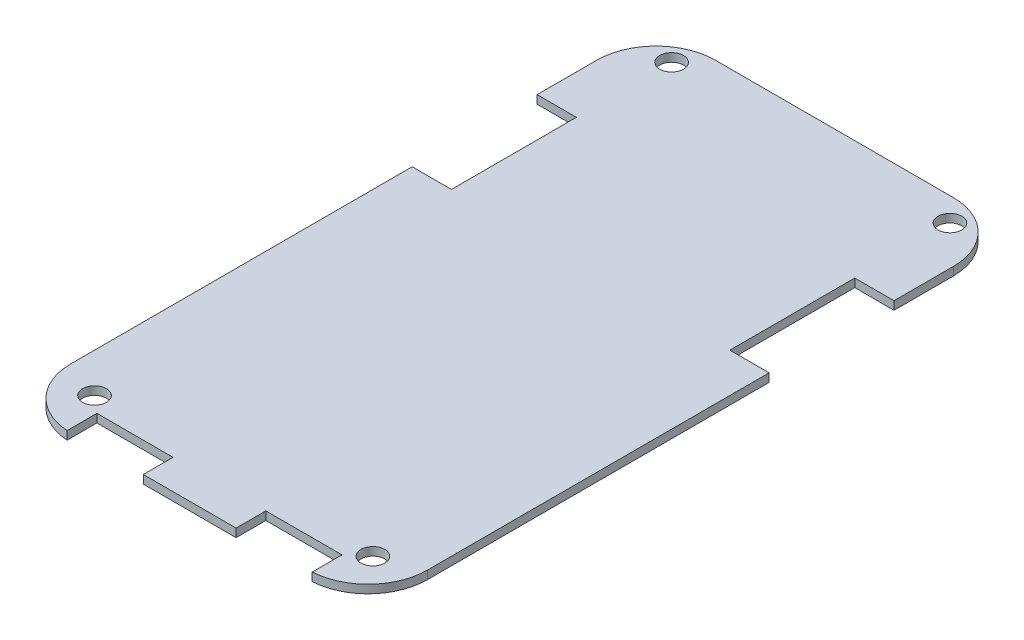
SolidWorks part; units mm, degrees
material "A-Glass Fiber"
ref_plane "Front Plane" through (0, 0, 0) normal (0, 0, 1) x (1, 0, 0)
ref_plane "Top Plane" through (0, 0, 0) normal (0, 1, 0) x (1, 0, 0)
ref_plane "Right Plane" through (0, 0, 0) normal (1, 0, 0) x (0, 0, -1)
sketch "Sketch2" plane through (0, 0, 0) normal (0, 1, 0) x (1, 0, 0)
  line L1 (-15, 27.1) -> (15, 27.1)
  line L2 (-15, 27.1) -> (-15, -27.1)
  line L3 (-15, -27.1) -> (15, -27.1)
  line L4 (15, 27.1) -> (15, -27.1)
  dimension "D1" = 30
  dimension "D2" = 54.2
  dimension "D3" = 15
  dimension "D4" = 27.1
extrude "CircuitBoard" add sketch "Sketch2" along normal blind 0.7
sketch "Sketch3" plane through (0, 0.7, 0) normal (0, 1, 0) x (1, 0, 0)
  line L0 (15, 27.1) -> (-15, 27.1) construction
  line L1 (-15, 17.1) -> (-11.7, 17.1)
  line L2 (-15, 17.1) -> (-15, 6.6)
  line L3 (-15, 6.6) -> (-11.7, 6.6)
  line L4 (-11.7, 17.1) -> (-11.7, 6.6)
  line L5 (-15, 27.1) -> (-15, -27.1) construction
  line L6 (-15, -27.1) -> (15, -27.1) construction
  line L7 (-10.3, -24.6) -> (-3.9, -24.6)
  line L8 (-10.3, -24.6) -> (-10.3, -27.1)
  line L9 (-10.3, -27.1) -> (-3.9, -27.1)
  line L10 (-3.9, -24.6) -> (-3.9, -27.1)
  dimension "D1" = 10.5
  dimension "D2" = 3.3
  dimension "D3" = 10
  dimension "D4" = 3.3
  dimension "D5" = 6.4
  dimension "D6" = 4.7
  dimension "D7" = 2.5
  dimension "D8" = 2.5
extrude "Cut-Extrude1" cut sketch "Sketch3" against normal through all
mirror "Cut_Mirror" about plane through (0, 0, 0) normal (1, 0, 0) of "Cut-Extrude1" second plane through (0, 0, 0) second plane normal (0, 1, 0)
fillet "Fillet2" radius 5 4 edges at (-15, 0.35, 27.1) (15, 0.35, 27.1) (15, 0.35, -27.1) (-15, 0.35, -27.1)
sketch "Sketch4" plane through (0, 0.7, 0) normal (0, 1, 0) x (1, 0, 0)
  line L0 (-15, 6.6) -> (-11.7, 6.6) construction
  circle A0 centre (-11.7, 25.1) radius 1
  circle A1 centre (-11.7, -23.4) radius 1
  dimension "D1" = 8
  dimension "D2" = 2
  dimension "D3" = 2
  dimension "D4" = 30
extrude "ScrewHoles" cut sketch "Sketch4" against normal through all
mirror "ScrewHoles_Mirror" about plane through (0, 0, 0) normal (1, 0, 0) of "ScrewHoles" second plane through (0, 0, 0) second plane normal (0, 1, 0)
